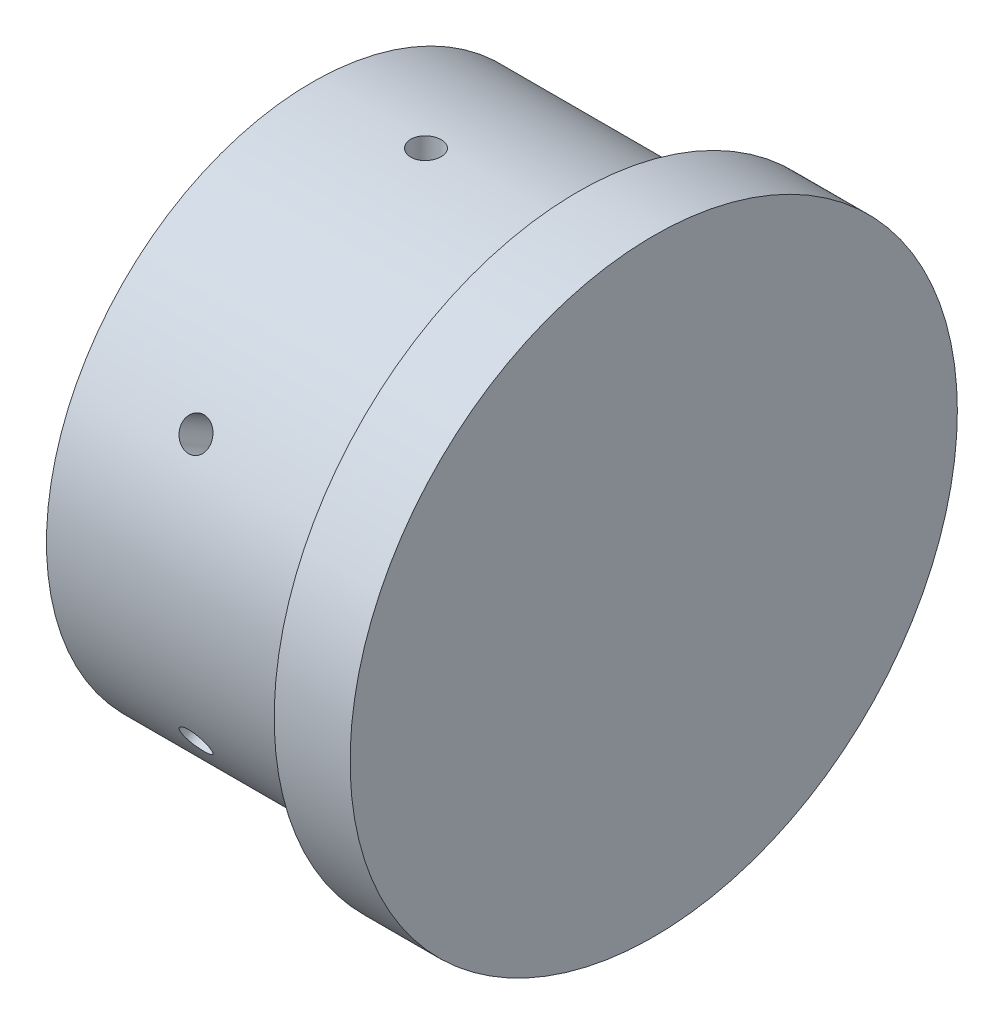
SolidWorks part; units mm, degrees
ref_plane "Front Plane" through (0, 0, 0) normal (0, 0, 1) x (1, 0, 0)
ref_plane "Top Plane" through (0, 0, 0) normal (0, 1, 0) x (1, 0, 0)
ref_plane "Right Plane" through (0, 0, 0) normal (1, 0, 0) x (0, 0, -1)
sketch "Sketch1" plane through (0, 0, 0) normal (1, 0, 0) x (0, 0, -1)
  circle A0 centre (0, 0) radius 35
  dimension "D1" = 70
extrude "Boss-Extrude1" add sketch "Sketch1" along normal blind 35
sketch "Sketch2" plane through (35, 0, 0) normal (1, 0, 0) x (0, 0, -1)
  circle A0 centre (0, 0) radius 40
  dimension "D1" = 80
extrude "Boss-Extrude2" add sketch "Sketch2" along normal blind 10
ref_plane "Bolts" through (0, 35, 0) normal (0, 1, 0) x (1, 0, 0)
sketch "Sketch3" plane through (0, 35, 0) normal (0, 1, 0) x (1, 0, 0)
  line L0 (35, 0) -> (15, 0) construction
  line L1 (35, 40) -> (35, -40) construction
  circle A0 centre (15, 0) radius 2
  dimension "D2" = 4
  dimension "D1" = 20
extrude "Cut-Extrude1" cut sketch "Sketch3" against normal blind 10
pattern_circular "CirPattern1" count 6 over 360 about axis through (35, 0, 0) along (-1, 0, 0) of "Cut-Extrude1" reverse direction yes
